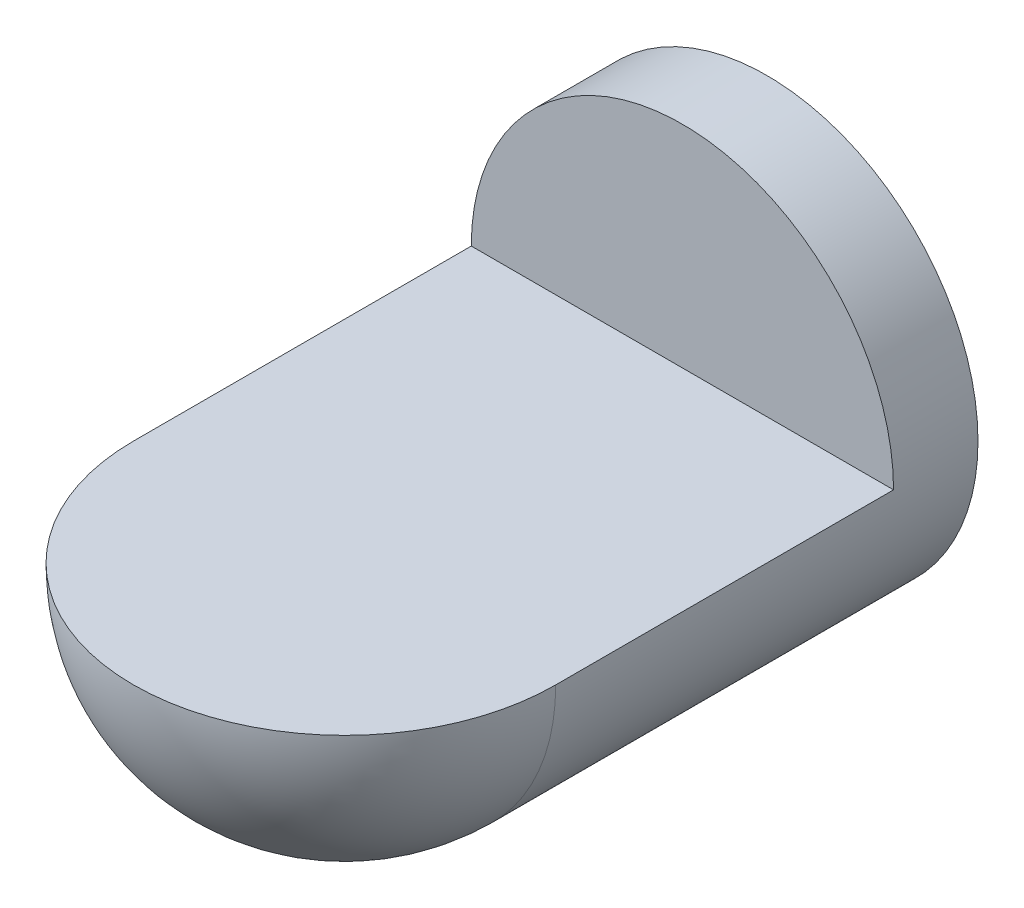
SolidWorks part; units mm, degrees
ref_plane "Front Plane" through (0, 0, 0) normal (0, 0, 1) x (1, 0, 0)
ref_plane "Top Plane" through (0, 0, 0) normal (0, 1, 0) x (1, 0, 0)
ref_plane "Right Plane" through (0, 0, 0) normal (1, 0, 0) x (0, 0, -1)
sketch "Sketch1" plane through (0, 0, 0) normal (1, 0, 0) x (0, 0, -1)
  line L0 (-146.9091, 0) -> (313.5945, 0) construction
  line L1 (150, 0) -> (-75, 0)
  line L2 (150, 0) -> (150, 75)
  line L3 (0, 75) -> (150, 75)
  arc A0 (-75, 0) -> (0, 75) centre (0, 0) cw
  dimension "D1" = 75
  dimension "D2" = 150
revolve "Revolve1" add sketch "Sketch1" angle 360 about L0
sketch "Sketch2" plane through (0, 0, 0) normal (1, 0, 0) x (0, 0, -1)
  line L0 (-88.0407, 0) -> (120.4455, 0) construction
  line L1 (120, 0) -> (120, 75)
  line L2 (150, 75) -> (0, 75) construction
  line L3 (120, 0) -> (-75, 0)
  line L4 (120, 75) -> (0, 75)
  line L5 (150, -75) -> (150, 75) construction
  arc A0 (0, 75) -> (0, -75) centre (0, 0) ccw construction
  arc A1 (-75, 0) -> (0, 75) centre (0, 0) cw
  dimension "D1" = 30
extrude "Cut-Extrude1" cut sketch "Sketch2" along normal through all and the other way through all
ref_axis "Axis1" through (0, 82.5, 0) along (0, -1, 0)
equation "\"link3_diameter\"=150"
equation "\"D1@Sketch1\"=\"link3_diameter\"/2"
equation "\"link3_length\"=150"
equation "\"D2@Sketch1\"=\"link3_length\""
equation "\"base_link_length\"=150"
equation "\"link1_diameter\"=150"
equation "\"link1_length\"=150"
equation "\"link2_diameter\"=150"
equation "\"link2_length\"=300"
equation "\"link4_diameter\"=150"
equation "\"link4_length\"=150"
equation "\"link5_diameter\"=150"
equation "\"link5_length\"=200"
equation "\"end_effector_diameter\"=150"
equation "\"end_effector_length\"=150"
equation "\"base_link_diameterA\"=200"
equation "\"base_link_diameterB\"=150"
equation "\"base_link_lengthA\"=50"
